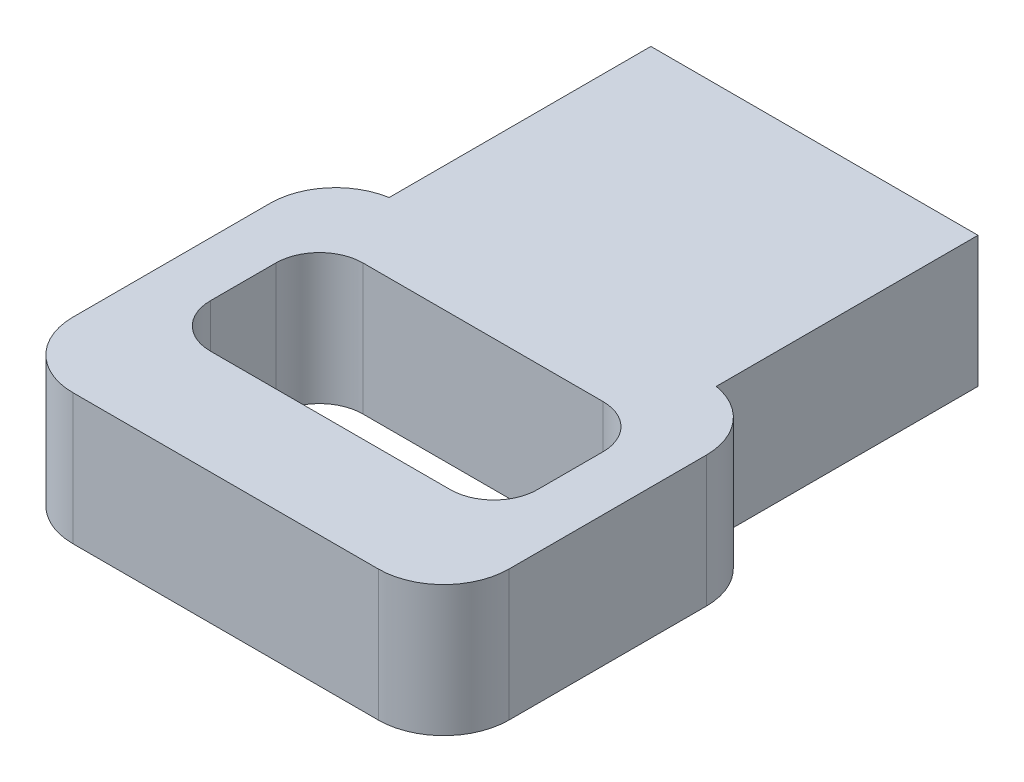
SolidWorks part; units mm, degrees
ref_plane "Front Plane" through (0, 0, 0) normal (0, 0, 1) x (1, 0, 0)
ref_plane "Top Plane" through (0, 0, 0) normal (0, 1, 0) x (1, 0, 0)
ref_plane "Right Plane" through (0, 0, 0) normal (1, 0, 0) x (0, 0, -1)
sketch "Sketch1" plane through (0, 0, 0) normal (0, 0, 1) x (1, 0, 0)
  line L1 (19.05, -7.62) -> (-19.05, -7.62)
  line L2 (19.05, -7.62) -> (19.05, 7.62)
  line L3 (19.05, 7.62) -> (-19.05, 7.62)
  line L4 (-19.05, -7.62) -> (-19.05, 7.62)
  line L5 (19.05, -7.62) -> (-19.05, 7.62) construction
  line L6 (19.05, 7.62) -> (-19.05, -7.62) construction
  point P0 (0, 0)
  dimension "D1" = 38.1
  dimension "D2" = 15.24
extrude "Boss-Extrude2" add sketch "Sketch1" along normal blind 30.48
sketch "Sketch2" plane through (0, 0, 30.48) normal (0, 0, 1) x (1, 0, 0)
  line L0 (19.05, 7.62) -> (-19.05, 7.62) construction
  line L1 (-25.4, -7.62) -> (25.4, -7.62)
  line L2 (-25.4, -7.62) -> (-25.4, 7.62)
  line L3 (-25.4, 7.62) -> (25.4, 7.62)
  line L4 (25.4, -7.62) -> (25.4, 7.62)
  line L5 (-25.4, -7.62) -> (25.4, 7.62) construction
  line L6 (-25.4, 7.62) -> (25.4, -7.62) construction
  point P0 (0, 0)
  dimension "D1" = 0
  dimension "D2" = 50.8
extrude "Boss-Extrude3" add sketch "Sketch2" along normal blind 38.1
sketch "Sketch3" plane through (0, -7.62, 0) normal (0, -1, 0) x (1, 0, 0)
  line L0 (0, 68.58) -> (0, 0) construction
  line L1 (-25.4, 68.58) -> (25.4, 68.58) construction
  line L3 (-19.05, 56.3844) -> (19.05, 56.3844)
  line L4 (-19.05, 56.3844) -> (-19.05, 38.6044)
  line L5 (-19.05, 38.6044) -> (19.05, 38.6044)
  line L6 (19.05, 56.3844) -> (19.05, 38.6044)
  line L7 (-19.05, 56.3844) -> (19.05, 38.6044) construction
  line L8 (-19.05, 38.6044) -> (19.05, 56.3844) construction
  point P5 (0, 47.4944)
  dimension "D1" = 17.78
extrude "Cut-Extrude1" cut sketch "Sketch3" against normal through all contours L3 L6 L5 L4
fillet "Fillet1" radius 5.08 4 edges at (19.05, 0, 38.6044) (-19.05, 0, 38.6044) (19.05, 0, 56.3844) (-19.05, 0, 56.3844)
fillet "Fillet2" radius 7.62 4 edges at (-25.4, 0, 30.48) (25.4, 0, 30.48) (25.4, 0, 68.58) (-25.4, 0, 68.58)
